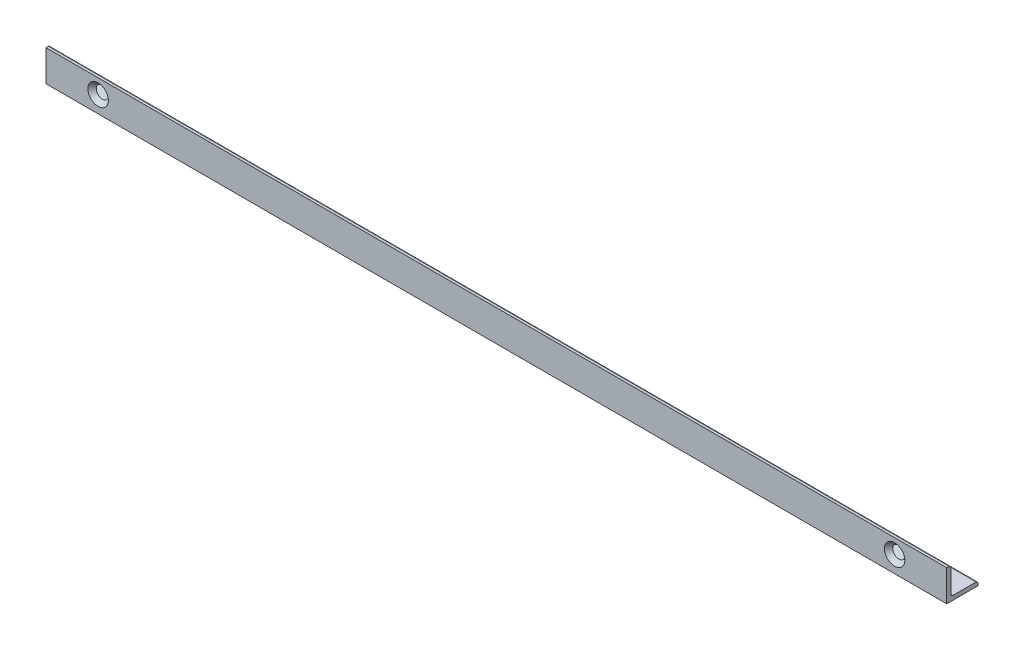
SolidWorks part; units mm, degrees
material "1060 Сплав"
ref_plane "Front" through (0, 0, 0) normal (0, 0, 1) x (1, 0, 0)
ref_plane "Top" through (0, 0, 0) normal (0, 1, 0) x (1, 0, 0)
ref_plane "Right" through (0, 0, 0) normal (1, 0, 0) x (0, 0, -1)
sketch "Эскиз1" plane through (0, 0, 0) normal (1, 0, 0) x (0, 0, -1)
  line L0 (0, 0) -> (0, 15)
  line L1 (0, 0) -> (15, 0)
  line L2 (0, 15) -> (1, 15)
  line L3 (2, 14) -> (2, 3)
  line L4 (3, 2) -> (14, 2)
  line L5 (15, 1) -> (15, 0)
  arc A0 (14, 2) -> (15, 1) centre (14, 1) cw
  arc A1 (1, 15) -> (2, 14) centre (1, 14) cw
  arc A2 (2, 3) -> (3, 2) centre (3, 3) ccw
  point P9 (15, 2)
  point P12 (2, 15)
  dimension "D5" = 1
  dimension "D1" = 15
  dimension "D2" = 15
  dimension "D3" = 2
  dimension "D4" = 2
extrude "Бобышка-Вытянуть1" add sketch "Эскиз1" along normal blind 432
sketch "Эскиз3" plane through (0, 0, -2) normal (0, 0, -1) x (-1, 0, 0)
  line L0 (-432, 3) -> (-432, 14) construction
  line L1 (-432, 15) -> (0, 15) construction
  line L2 (0, 3) -> (0, 14) construction
  circle A0 centre (-407, 8) radius 2.8
  circle A1 centre (-25, 8) radius 2.8
  dimension "D1" = 5.6
  dimension "D2" = 25
  dimension "D3" = 7
  dimension "D4" = 5.6
  dimension "D5" = 7
  dimension "D6" = 25
extrude "Вырез-Вытянуть2" cut sketch "Эскиз3" against normal through all
sketch "Эскиз4" plane through (0, 0, 0) normal (0, -1, 0) x (1, 0, 0)
  line L0 (432, -15) -> (0, -15) construction
  line L1 (0, 0) -> (0, -15) construction
  line L2 (432, 0) -> (432, -15) construction
  circle A0 centre (367, -8) radius 2.25
  circle A2 centre (65, -8) radius 2.25
  dimension "D1" = 4.5
  dimension "D2" = 7
  dimension "D3" = 65
  dimension "D4" = 4.5
  dimension "D5" = 65
  dimension "D6" = 7
extrude "Вырез-Вытянуть3" cut sketch "Эскиз4" against normal blind 2
chamfer "Фаска1" distance 2.05 angle 45 2 edges at (65, 0, -10.25) (367, 0, -10.25)
chamfer "Фаска2" distance 2.098 angle 45 2 edges at (407, 10.8, 0) (25, 10.8, 0)
sketch "Эскиз5" [suppressed] plane through (0, 2, 0) normal (0, 1, 0) x (1, 0, 0)
  line L0 (432, 14) -> (432, 3) construction
  line L1 (432, 15) -> (0, 15) construction
  line L2 (0, 14) -> (0, 3) construction
  circle A0 centre (392, 8) radius 2.3
  circle A1 centre (40, 8) radius 2.3
  dimension "D1" = 4.6
  dimension "D2" = 40
  dimension "D3" = 7
  dimension "D4" = 4.6
  dimension "D5" = 7
  dimension "D6" = 40
extrude "Вырез-Вытянуть4" [suppressed] cut sketch "Эскиз5" against normal through all
chamfer "Фаска3" [suppressed] distance 2.05 angle 45
